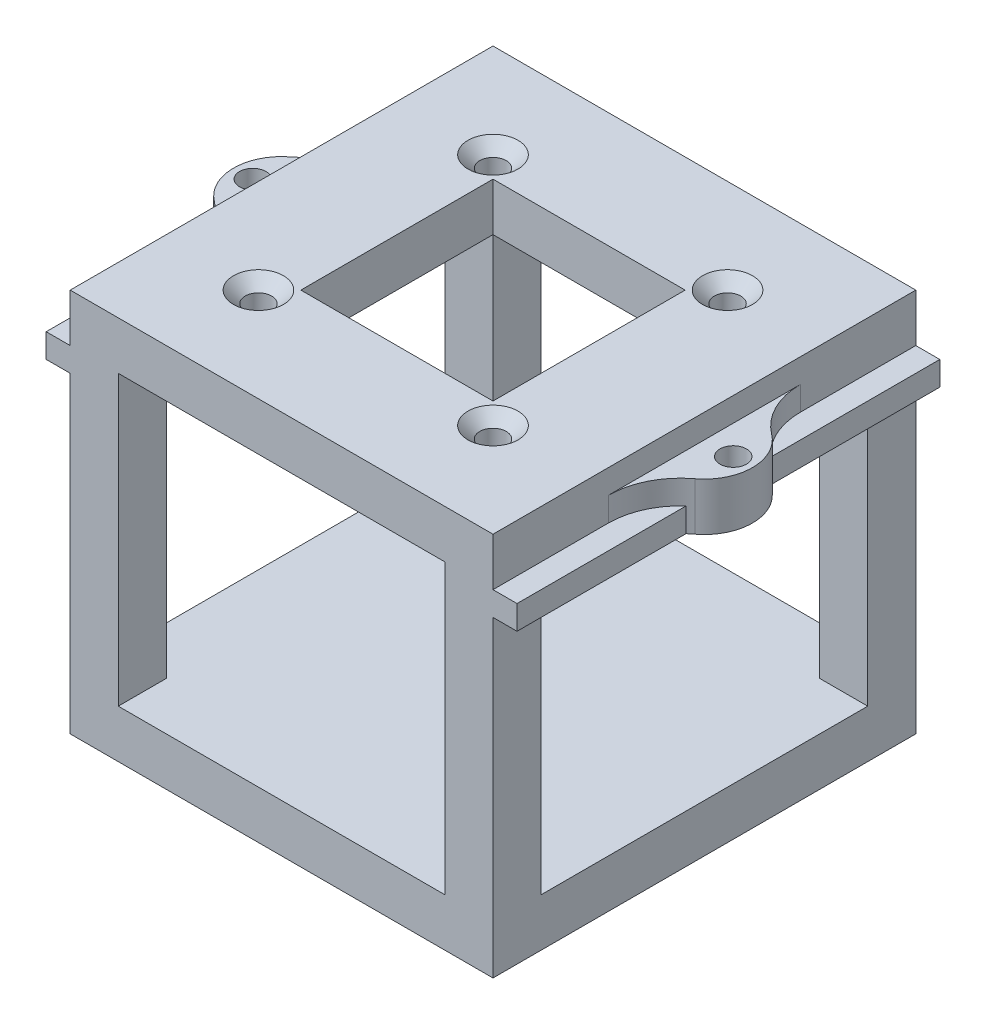
SolidWorks part; units mm, degrees
ref_plane "Front Plane" through (0, 0, 0) normal (0, 0, 1) x (1, 0, 0)
ref_plane "Top Plane" through (0, 0, 0) normal (0, 1, 0) x (1, 0, 0)
ref_plane "Right Plane" through (0, 0, 0) normal (1, 0, 0) x (0, 0, -1)
sketch "Sketch1" plane through (0, 0, 0) normal (0, 1, 0) x (1, 0, 0)
  line L1 (0, 0) -> (55.88, 0)
  line L2 (0, 0) -> (0, 55.88)
  line L3 (0, 55.88) -> (55.88, 55.88)
  line L4 (55.88, 0) -> (55.88, 55.88)
  dimension "D1" = 55.88
  dimension "D2" = 55.88
extrude "Boss-Extrude1" add sketch "Sketch1" along normal blind 50.8
sketch "Sketch2" plane through (0, 0, 0) normal (0, 0, 1) x (1, 0, 0)
  line L0 (0, 50.8) -> (55.88, 50.8) construction
  line L1 (6.35, 6.35) -> (49.53, 6.35)
  line L2 (6.35, 6.35) -> (6.35, 44.45)
  line L3 (6.35, 44.45) -> (49.53, 44.45)
  line L4 (49.53, 6.35) -> (49.53, 44.45)
  line L5 (0, 50.8) -> (0, 0) construction
  line L6 (0, 0) -> (55.88, 0) construction
  line L7 (0, 50.8) -> (0, 0) construction
  point P4 (27.94, 44.45)
  point P7 (27.94, 50.8)
  point P8 (6.35, 25.4)
  point P11 (0, 25.4)
  dimension "D1" = 6.35
  dimension "D2" = 6.35
extrude "Cut-Extrude1" cut sketch "Sketch2" against normal through all
sketch "Sketch3" plane through (55.88, 0, 0) normal (1, 0, 0) x (0, 0, -1)
  line L0 (0, 50.8) -> (55.88, 50.8) construction
  line L1 (6.35, 6.35) -> (49.53, 6.35)
  line L2 (6.35, 6.35) -> (6.35, 44.45)
  line L3 (6.35, 44.45) -> (49.53, 44.45)
  line L4 (49.53, 6.35) -> (49.53, 44.45)
  line L5 (0, 50.8) -> (0, 0) construction
  point P4 (27.94, 44.45)
  point P7 (27.94, 50.8)
  point P8 (6.35, 25.4)
  point P11 (0, 25.4)
  dimension "D1" = 6.35
  dimension "D2" = 6.35
extrude "Cut-Extrude2" cut sketch "Sketch3" against normal through all
sketch "Sketch4" plane through (0, 50.8, 0) normal (0, 1, 0) x (1, 0, 0)
  line L0 (55.88, 0) -> (55.88, 55.88) construction
  line L6 (12.44, 49.09) -> (43.44, 49.09) construction
  line L7 (43.44, 49.09) -> (49.09, 43.44) construction
  line L8 (49.09, 43.44) -> (49.09, 12.44) construction
  line L9 (49.09, 12.44) -> (43.44, 6.79) construction
  line L10 (43.44, 6.79) -> (12.44, 6.79) construction
  line L11 (12.44, 6.79) -> (6.79, 12.44) construction
  line L12 (6.79, 12.44) -> (6.79, 43.44) construction
  line L13 (6.79, 43.44) -> (12.44, 49.09) construction
  line L14 (55.88, 55.88) -> (0, 55.88) construction
  line L15 (46.265, 9.615) -> (9.615, 46.265) construction
  line L16 (15.24, 40.64) -> (40.64, 40.64)
  line L17 (15.24, 40.64) -> (15.24, 15.24)
  line L18 (15.24, 15.24) -> (40.64, 15.24)
  line L19 (40.64, 40.64) -> (40.64, 15.24)
  line L20 (46.265, 46.265) -> (9.615, 9.615) construction
  circle A0 centre (43.44, 43.44) radius 1.75
  circle A1 centre (43.44, 12.44) radius 1.75
  circle A2 centre (12.44, 12.44) radius 1.75
  circle A3 centre (12.44, 43.44) radius 1.75
  point P7 (55.88, 27.94)
  point P16 (49.09, 27.94)
  point P17 (27.94, 49.09)
  point P20 (27.94, 55.88)
  dimension "D3" = 3.5
  dimension "D1" = 42.3
  dimension "D2" = 31
  dimension "D4" = 25.4
extrude "Cut-Extrude3" cut sketch "Sketch4" against normal up to surface (44.45 mm away) up to face at (27.94, 6.35, -27.94)
ref_axis "Axis1" through (12.44, 44.45, -12.44) along (0, 1, 0)
ref_axis "Axis2" through (12.44, 44.45, -43.44) along (0, 1, 0)
ref_axis "Axis3" through (43.44, 44.45, -43.44) along (0, 1, 0)
ref_axis "Axis4" through (43.44, 44.45, -12.44) along (0, 1, 0)
ref_plane "Plane1" through (43.44, 0, 0) normal (1, 0, 0) x (0, 0, -1)
ref_plane "Plane2" through (12.44, 0, 0) normal (1, 0, 0) x (0, 0, -1)
sketch "Sketch5" plane through (12.44, 0, 0) normal (1, 0, 0) x (0, 0, -1)
  line L0 (43.44, 50.8) -> (40.138, 50.8)
  line L1 (40.138, 50.8) -> (43.44, 47.498)
  line L2 (43.44, 47.498) -> (43.44, 50.8)
  line L3 (43.44, 44.45) -> (43.44, 50.8) construction
  line L4 (45.19, 50.8) -> (41.69, 50.8) construction
  dimension "D1" = 3.302
  dimension "D2" = 3.302
revolve "Cut-Revolve1" cut sketch "Sketch5" angle 360 about L2
sketch "Sketch6" plane through (12.44, 0, 0) normal (1, 0, 0) x (0, 0, -1)
  line L0 (12.44, 50.8) -> (9.138, 50.8)
  line L1 (9.138, 50.8) -> (12.44, 47.498)
  line L2 (12.44, 47.498) -> (12.44, 50.8)
  line L3 (12.44, 44.45) -> (12.44, 50.8) construction
  line L4 (46.742, 50.8) -> (40.138, 50.8) construction
  dimension "D1" = 3.302
  dimension "D2" = 3.302
revolve "Cut-Revolve2" cut sketch "Sketch6" angle 360 about L2
sketch "Sketch7" plane through (43.44, 0, 0) normal (1, 0, 0) x (0, 0, -1)
  line L0 (43.44, 50.8) -> (40.138, 50.8)
  line L1 (40.138, 50.8) -> (43.44, 47.498)
  line L2 (43.44, 47.498) -> (43.44, 50.8)
  line L3 (43.44, 44.45) -> (43.44, 50.8) construction
  line L4 (15.742, 50.8) -> (9.138, 50.8) construction
  dimension "D1" = 3.302
  dimension "D2" = 3.302
revolve "Cut-Revolve3" cut sketch "Sketch7" angle 360 about L2
sketch "Sketch8" plane through (43.44, 0, 0) normal (1, 0, 0) x (0, 0, -1)
  line L0 (12.44, 50.8) -> (9.138, 50.8)
  line L1 (9.138, 50.8) -> (12.44, 47.498)
  line L2 (12.44, 47.498) -> (12.44, 50.8)
  line L3 (12.44, 44.45) -> (12.44, 50.8) construction
  line L4 (46.742, 50.8) -> (40.138, 50.8) construction
  dimension "D1" = 3.302
  dimension "D2" = 3.302
revolve "Cut-Revolve4" cut sketch "Sketch8" angle 360 about L2
sketch "Sketch9" plane through (0, 44.45, 0) normal (0, -1, 0) x (1, 0, 0)
  line L0 (0, -49.53) -> (0, -6.35) construction
  line L1 (0, -40.64) -> (0, -15.24)
  line L2 (27.94, 0) -> (27.94, -55.88) construction
  line L3 (49.53, 0) -> (6.35, 0) construction
  line L4 (49.53, -55.88) -> (6.35, -55.88) construction
  line L5 (55.88, -40.64) -> (55.88, -15.24)
  line L6 (0, -27.94) -> (55.88, -27.94) construction
  arc A0 (0, -15.24) -> (-3.81, -22.86) centre (-9.525, -15.24) cw
  arc A1 (-3.81, -22.86) -> (-3.81, -33.02) centre (0, -27.94) ccw
  arc A2 (-3.81, -33.02) -> (0, -40.64) centre (-9.525, -40.64) cw
  arc A3 (59.69, -33.02) -> (55.88, -40.64) centre (65.405, -40.64) ccw
  arc A4 (59.69, -22.86) -> (59.69, -33.02) centre (55.88, -27.94) cw
  arc A5 (55.88, -15.24) -> (59.69, -22.86) centre (65.405, -15.24) ccw
  point P11 (-6.35, -27.94)
  dimension "D1" = 6.35
  dimension "D2" = 25.4
extrude "Boss-Extrude2" add sketch "Sketch9" along normal blind 3.175 and the other way blind 3.175
sketch "Sketch10" plane through (0, 0, 0) normal (0, 0, 1) x (1, 0, 0)
  line L1 (49.53, 44.45) -> (59.055, 44.45)
  line L2 (49.53, 44.45) -> (49.53, 41.275)
  line L3 (49.53, 41.275) -> (59.055, 41.275)
  line L4 (59.055, 44.45) -> (59.055, 41.275)
  line L5 (49.53, 44.45) -> (6.35, 44.45) construction
  line L6 (27.94, 50.8) -> (27.94, 0) construction
  line L7 (0, 50.8) -> (55.88, 50.8) construction
  line L8 (0, 0) -> (55.88, 0) construction
  line L9 (6.35, 41.275) -> (-3.175, 41.275)
  line L10 (-3.175, 44.45) -> (-3.175, 41.275)
  line L11 (6.35, 44.45) -> (-3.175, 44.45)
  line L12 (6.35, 44.45) -> (6.35, 41.275)
  line L13 (49.53, 6.35) -> (49.53, 44.45) construction
  line L14 (55.88, 50.8) -> (55.88, 0) construction
  dimension "D1" = 3.175
extrude "Boss-Extrude5" add sketch "Sketch10" against normal up to surface (55.88 mm away) up to face at (27.94, 25.4, -55.88)
sketch "Sketch11" plane through (0, 47.625, 0) normal (0, 1, 0) x (1, 0, 0)
  line L0 (-3.81, 33.02) -> (-3.81, 22.86) construction
  line L1 (59.69, 22.86) -> (59.69, 33.02) construction
  circle A0 centre (-3.81, 27.94) radius 1.75
  arc A1 (59.69, 22.86) -> (59.69, 33.02) centre (55.88, 27.94) ccw construction
  circle A2 centre (59.69, 27.94) radius 1.75
  dimension "D1" = 3.5
  dimension "D2" = 3.5
extrude "Cut-Extrude4" cut sketch "Sketch11" against normal through all
